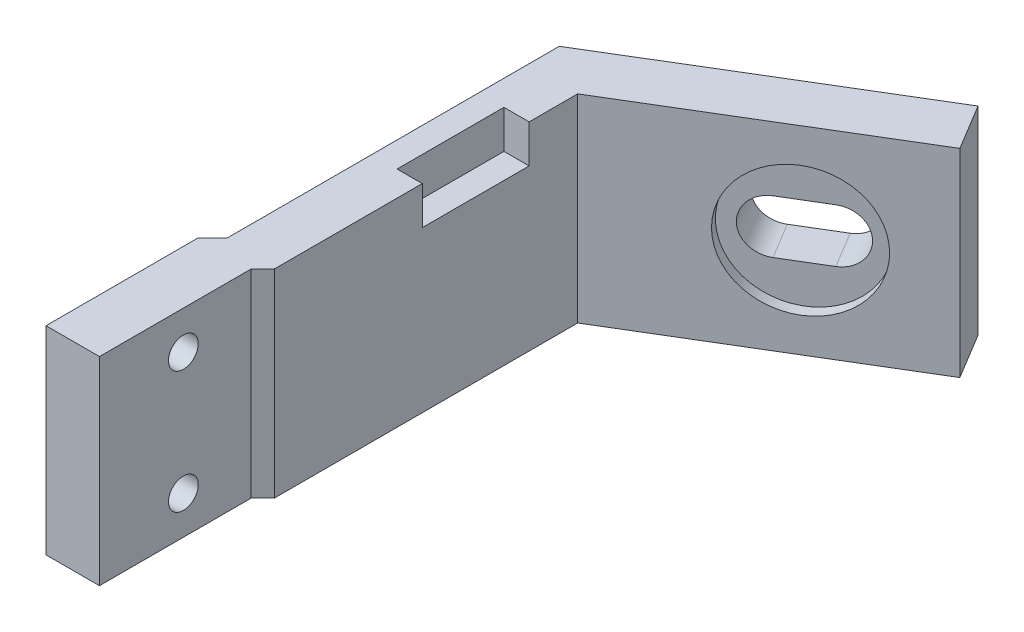
SolidWorks part; units mm, degrees
ref_plane "Front Plane" through (0, 0, 0) normal (0, 0, 1) x (1, 0, 0)
ref_plane "Top Plane" through (0, 0, 0) normal (0, 1, 0) x (1, 0, 0)
ref_plane "Right Plane" through (0, 0, 0) normal (1, 0, 0) x (0, 0, -1)
ref_plane "PY -20.700" through (0, -20.7, 0) normal (0, 1, 0) x (1, 0, 0)
sketch "leg and pad sketch" plane through (0, -20.7, 0) normal (0, 1, 0) x (1, 0, 0)
  line L0 (-0.4, 29.7586) -> (-0.4, -9.98)
  line L1 (-0.4, -9.98) -> (-1.92, -11.5)
  line L2 (-1.92, -11.5) -> (-1.92, -31.37)
  line L3 (-1.92, -31.37) -> (-8.92, -31.37)
  line L4 (-8.92, -31.37) -> (-8.92, -11.5)
  line L5 (-8.92, -11.5) -> (-7, -9.58)
  line L6 (-7, -9.58) -> (-7, 33.9514)
  line L7 (-7, 33.9514) -> (27.2048, 54.5947)
  line L8 (27.2048, 54.5947) -> (30.8218, 48.6015)
  line L9 (30.8218, 48.6015) -> (-0.4, 29.7586)
extrude "leg and pad" add sketch "leg and pad sketch" along normal mid plane 26
ref_plane "PX -1.350" through (-1.35, 0, 0) normal (1, 0, 0) x (0, 0, -1)
sketch "screw head relief sketch" plane through (-1.35, 0, 0) normal (1, 0, 0) x (0, 0, -1)
  line L0 (23.4, -12.7) -> (23.4, -6.7)
  line L1 (23.4, -6.7) -> (9.4, -6.7)
  line L2 (9.4, -6.7) -> (9.4, -12.7)
  line L3 (9.4, -12.7) -> (23.4, -12.7)
extrude "screw head relief" cut sketch "screw head relief sketch" against normal mid plane 4.7
sketch "insert flange relief sketch" plane through (0, -20.7, 0) normal (0, 1, 0) x (1, 0, 0)
  line L0 (18.3249, 39.8914) -> (17.0331, 42.0318)
  line L1 (17.0331, 42.0318) -> (9.7557, 37.6398)
  line L2 (9.7557, 37.6398) -> (11.0475, 35.4994)
  line L3 (11.0475, 35.4994) -> (18.3249, 39.8914)
revolve "insert flange relief" cut sketch "insert flange relief sketch" angle 360 about L0
sketch "M6 slot end 1 sketch" plane through (0, -20.7, 0) normal (0, 1, 0) x (1, 0, 0)
  line L0 (20.8933, 41.4415) -> (16.243, 49.147)
  line L1 (16.243, 49.147) -> (13.2464, 47.3385)
  line L2 (13.2464, 47.3385) -> (17.8968, 39.633)
  line L3 (17.8968, 39.633) -> (20.8933, 41.4415)
revolve "M6 slot end 1" cut sketch "M6 slot end 1 sketch" angle 360 about L0
sketch "M6 slot end 2 sketch" plane through (0, -20.7, 0) normal (0, 1, 0) x (1, 0, 0)
  line L0 (15.7564, 38.3413) -> (11.106, 46.0467)
  line L1 (11.106, 46.0467) -> (8.1094, 44.2382)
  line L2 (8.1094, 44.2382) -> (12.7598, 36.5328)
  line L3 (12.7598, 36.5328) -> (15.7564, 38.3413)
revolve "M6 slot end 2" cut sketch "M6 slot end 2 sketch" angle 360 about L0
sketch "M6 slot middle sketch" plane through (0, -20.7, 0) normal (0, 1, 0) x (1, 0, 0)
  line L0 (15.7564, 38.3413) -> (20.8933, 41.4415)
  line L1 (20.8933, 41.4415) -> (16.243, 49.147)
  line L2 (16.243, 49.147) -> (11.106, 46.0467)
  line L3 (11.106, 46.0467) -> (15.7564, 38.3413)
extrude "M6 slot middle" cut sketch "M6 slot middle sketch" against normal mid plane 7
ref_plane "PX -5.420" through (-5.42, 0, 0) normal (1, 0, 0) x (0, 0, -1)
sketch "screw holes sketch" plane through (-5.42, 0, 0) normal (1, 0, 0) x (0, 0, -1)
  circle A0 centre (-20.375, -28.7) radius 1.95
  circle A1 centre (-20.375, -12.7) radius 1.95
extrude "screw holes" cut sketch "screw holes sketch" against normal mid plane 9
equation "\"diffL\" = 608.8mm"
equation "\"diffW\" = 329.4mm"
equation "\"diffT\" = 2.9mm"
equation "\"chanSlotW\" = 12.9mm"
equation "\"chanSlotDepth\" = 11.13mm"
equation "\"chanFloor\" = 1.57mm"
equation "\"chanLeg\" = 12.7mm"
equation "\"lightL\" = 605mm"
equation "\"lightW\" = 331mm"
equation "\"lightH\" = 92mm"
equation "\"lightSideFlat\" = 30mm"
equation "\"lightSlopeLen\" = 33.1mm"
equation "\"lightWingDepth\" = 47.9mm"
equation "\"lightWingFlat\" = 90.2mm"
equation "\"lightChanW\" = 99.6mm"
equation "\"lightChanStand\" = 44.1mm"
equation "\"insFlangeD\" = 12.3mm"
equation "\"insFromEnd\" = 20.7mm"
equation "\"insUpSlope\" = 20.8mm"
equation "\"gaugeH\" = 10mm"
equation "\"gaugeStepLen\" = 14mm"
equation "\"gaugeStepW0\" = 13.1mm"
equation "\"gaugeStepDW\" = 0.2mm"
equation "\"gaugeSteps\" = 5mm"
equation "\"gaugeHandleLen\" = 30mm"
equation "\"gaugeHandleW\" = 24mm"
equation "\"gaugeSlot0\" = 3mm"
equation "\"gaugeSlotD\" = 0.1mm"
equation "\"gaugeSlotDepth\" = 8mm"
equation "\"gap\" = 25.4mm"
equation "\"edgeL\" = 1mm"
equation "\"edgeW\" = 0.75mm"
equation "\"proud\" = 1.5mm"
equation "\"seatClr\" = 0.15mm"
equation "\"tongueClrZ\" = 0.1mm"
equation "\"tongueClrX\" = 0.25mm"
equation "\"tongueLen\" = 30mm"
equation "\"armSide\" = 45mm"
equation "\"armEnd\" = 20mm"
equation "\"cornerCham\" = 3mm"
equation "\"brkW\" = 26mm"
equation "\"brkT\" = 7mm"
equation "\"brkSeatClr\" = 0.2mm"
equation "\"brkScrewSpan\" = 16mm"
equation "\"pilotD\" = 2.7mm"
equation "\"pilotDepth\" = 10mm"
equation "\"screwClrD\" = 3.9mm"
equation "\"jogBelow\" = 4mm"
equation "\"padT\" = 7mm"
equation "\"padLen\" = 31mm"
equation "\"m6Clr\" = 7mm"
equation "\"m6Slot\" = 3mm"
equation "\"flangeRelD\" = 17mm"
equation "\"flangeRelDepth\" = 1.5mm"
equation "\"relLen\" = 7mm"
equation "\"relDepth\" = 4mm"
equation "\"relLand\" = 2mm"
equation "\"knockN\" = 100mm"
equation "\"petgcfE\" = 3000mm"
equation "\"mockExtent\" = 110mm"
equation "\"relZnear\" = 9.4mm"
equation "\"relZfar\" = 23.4mm"
equation "\"headD\" = 8mm"
equation "\"headH\" = 2.5mm"
equation "\"headFromEnd\" = 6.8mm"
equation "\"headBack\" = 16.4mm"
equation "\"sideClr\" = 0.4mm"
